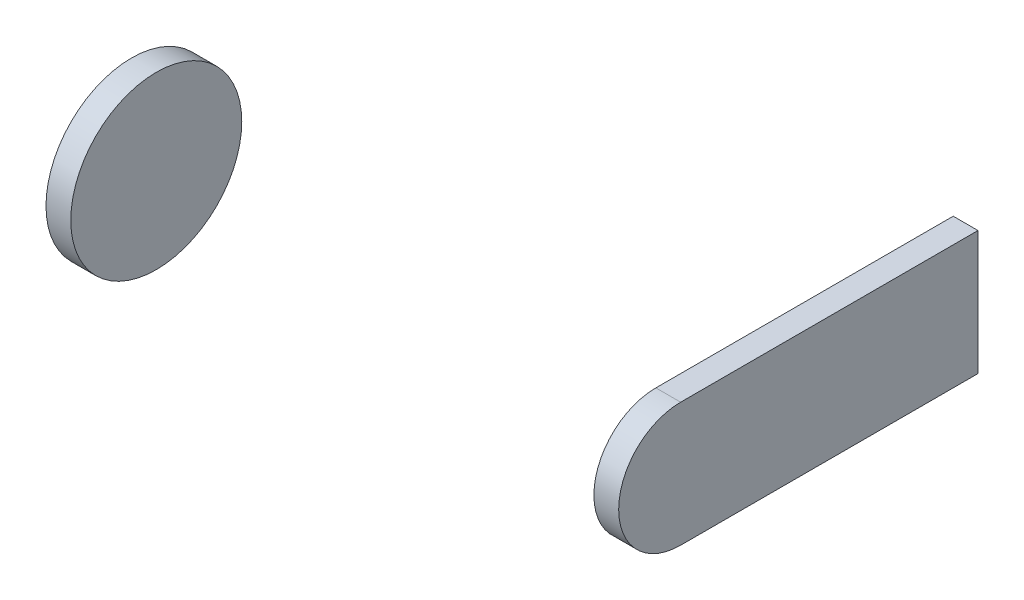
SolidWorks part; units mm, degrees
ref_plane "Front Plane" through (0, 0, 0) normal (0, 0, 1) x (1, 0, 0)
ref_plane "Top Plane" through (0, 0, 0) normal (0, 1, 0) x (1, 0, 0)
ref_plane "Right Plane" through (0, 0, 0) normal (1, 0, 0) x (0, 0, -1)
sketch "Sketch1" plane through (-30.7977, 0, 0) normal (-1, 0, 0) x (0, 0, 1)
  circle A1 centre (55.7761, 32.2775) radius 17.25
  circle A2 centre (55.7761, 32.2775) radius 17.25
  dimension "D1" = 0
extrude "Motor plate" add sketch "Sketch1" along normal blind 5
ref_plane "Plane1" through (70.0023, 0, 0) normal (1, 0, 0) x (0, 0, -1)
sketch "Sketch2" plane through (70.0023, 0, 0) normal (1, 0, 0) x (0, 0, -1)
  circle A0 centre (-55.7761, 32.2775) radius 12.5
  circle A1 centre (-55.7761, 32.2775) radius 8 construction
  dimension "D1" = 25
extrude "Bearing side" add sketch "Sketch2" along normal blind 5 separate body
sketch "Sketch3" plane through (70.0023, 0, 0) normal (-1, 0, 0) x (0, 0, 1)
  circle A0 centre (55.7761, 32.2775) radius 5
  circle A1 centre (55.7761, 32.2775) radius 12.5 construction
  dimension "D1" = 10
extrude "Bearing nub (only contacts inner hub of bearing)" add sketch "Sketch3" along normal blind 1.5
fillet "Bearing nub fillet 5mm" radius 5 1 edges at (70.0023, 27.2775, 55.7761)
sketch "Sketch4" plane through (75.0023, 0, 0) normal (1, 0, 0) x (0, 0, -1)
  line L0 (-55.7761, 44.7775) -> (4.2239, 44.7775)
  line L1 (4.2239, 44.7775) -> (4.2239, 19.7775)
  line L2 (4.2239, 19.7775) -> (-55.7761, 19.7775)
  circle A1 centre (-55.7761, 32.2775) radius 12.5
  arc A2 (-55.7761, 44.7775) -> (-55.7761, 19.7775) centre (-55.7761, 32.2775) ccw
  dimension "D2" = 60
  dimension "D1" = 0
extrude "Boss-Extrude4" add sketch "Sketch4" against normal blind 5
